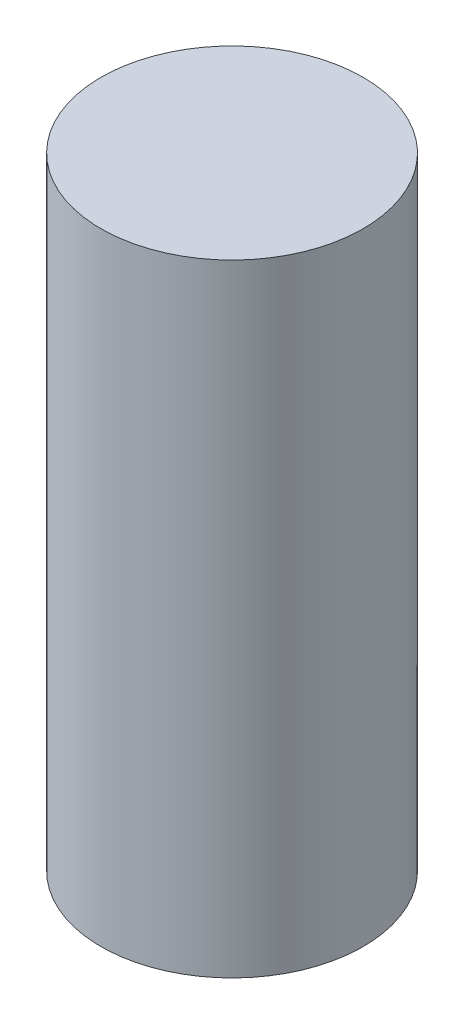
SolidWorks part; units mm, degrees
ref_plane "Front Plane" through (0, 0, 0) normal (0, 0, 1) x (1, 0, 0)
ref_plane "Top Plane" through (0, 0, 0) normal (0, 1, 0) x (1, 0, 0)
ref_plane "Right Plane" through (0, 0, 0) normal (1, 0, 0) x (0, 0, -1)
sketch "Sketch1" plane through (0, 0, 0) normal (0, 1, 0) x (1, 0, 0)
  circle A0 centre (0, 0) radius 12.7
  dimension "D1" = 25.4
extrude "Boss-Extrude1" add sketch "Sketch1" along normal blind 60.212
